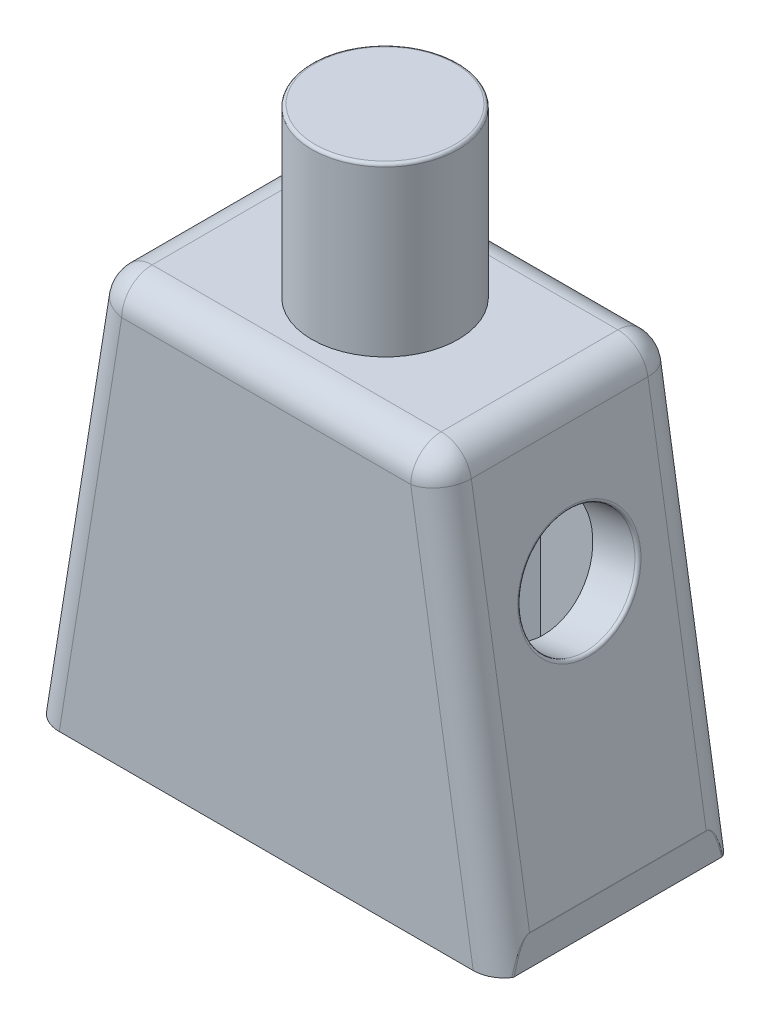
SolidWorks part; units mm, degrees
ref_plane "Front Plane" through (0, 0, 0) normal (0, 0, 1) x (1, 0, 0)
ref_plane "Top Plane" through (0, 0, 0) normal (0, 1, 0) x (1, 0, 0)
ref_plane "Right Plane" through (0, 0, 0) normal (1, 0, 0) x (0, 0, -1)
sketch "Sketch2" plane through (0, 0, 0) normal (0, 0, 1) x (1, 0, 0)
  line L0 (0, 0) -> (0, 13.8) construction
  line L1 (7.65, 0) -> (-7.65, 0)
  line L2 (-7.65, 0) -> (-7.65, 1)
  line L3 (-7.65, 1) -> (-5.6, 13.8)
  line L4 (-5.6, 13.8) -> (5.6, 13.8)
  line L5 (7.65, 0) -> (7.65, 1)
  line L6 (7.65, 1) -> (5.6, 13.8)
  dimension "D1" = 1
  dimension "D2" = 13.8
  dimension "D3" = 11.2
  dimension "D4" = 15.3
extrude "Torso" add sketch "Sketch2" along normal mid plane 7.8
shell "Shell1" thickness 1.5 removed face at (0, 0, 0)
sketch "Sketch3" plane through (-7.6148, 1.2196, 0) normal (-0.9874, 0.1581, 0) x (0, 0, 1)
  line L0 (0, 0) -> (0, 12.7408) construction
  line L1 (3.9, 12.7408) -> (-3.9, 12.7408) construction
  line L2 (3.9, -1.2098) -> (-3.9, -1.2098) construction
  circle A0 centre (0, 7.7902) radius 1.9
  dimension "D1" = 3.8
  dimension "D2" = 9
extrude "Arm Hole" cut sketch "Sketch3" against normal up to next
mirror "Mirror1" about plane through (0, 0, 0) normal (1, 0, 0) of "Arm Hole"
sketch "Sketch4" plane through (0, 0, 0) normal (0, -1, 0) x (1, 0, 0)
  line L0 (0, 3.9) -> (0, -3.9) construction
  line L1 (-7.65, 3.9) -> (7.65, 3.9) construction
  line L2 (-7.65, -3.9) -> (7.65, -3.9) construction
  line L3 (-2.7, 2.4) -> (-1.5, 2.4)
  line L4 (4.3211, 2.4) -> (-4.3211, 2.4) construction
  line L5 (-1.5, 2.4) -> (-1.5, 1.6)
  line L6 (-1.5, 1.6) -> (-2.7, 2.4)
  line L7 (1.5, 1.6) -> (2.7, 2.4)
  line L8 (2.7, 2.4) -> (1.5, 2.4)
  line L9 (1.5, 2.4) -> (1.5, 1.6)
  dimension "D1" = 3
  dimension "D2" = 1.2
  dimension "D3" = 0.8
extrude "Hip Ribs" add sketch "Sketch4" against normal up to next
mirror "Mirror2" about plane through (0, 0, 0) normal (0, 0, 1) of "Hip Ribs"
sketch "Sketch5" plane through (0, 13.8, 0) normal (0, 1, 0) x (1, 0, 0)
  circle A0 centre (0, 0) radius 2.4
  dimension "D1" = 4.8
extrude "Neck" add sketch "Sketch5" along normal blind 5.5
sketch "Sketch6" plane through (0, 12.3, 0) normal (0, -1, 0) x (1, 0, 0)
  circle A0 centre (0, 0) radius 1.25
  dimension "D1" = 2.5
extrude "Neck Inner" cut sketch "Sketch6" against normal blind 4.25
fillet "Fillet1" radius 1 4 edges at (-6.625, 7.4, -3.9) (6.625, 7.4, -3.9) (6.625, 7.4, 3.9) (-6.625, 7.4, 3.9)
fillet "Fillet2" radius 1 8 edges at (-5.3034, 13.8, 3.6071) (0, 13.8, 3.9) (5.3034, 13.8, 3.6071) (5.6, 13.8, 0) (5.3034, 13.8, -3.6071) (0, 13.8, -3.9) (-5.3034, 13.8, -3.6071) (-5.6, 13.8, 0)
fillet "Fillet3" radius 0.1 9 edges at (-7.65, 0.7449, 3.1812) (-7.65, 0.7449, -3.1812) (7.65, 0.7449, 3.1812) (7.65, 0.7449, -3.1812) (-7.65, 1, 0) (7.65, 1, 0) (0, 19.3, 2.4) (6.6834, 7.0357, 0) (-6.6834, 7.0357, 0)
